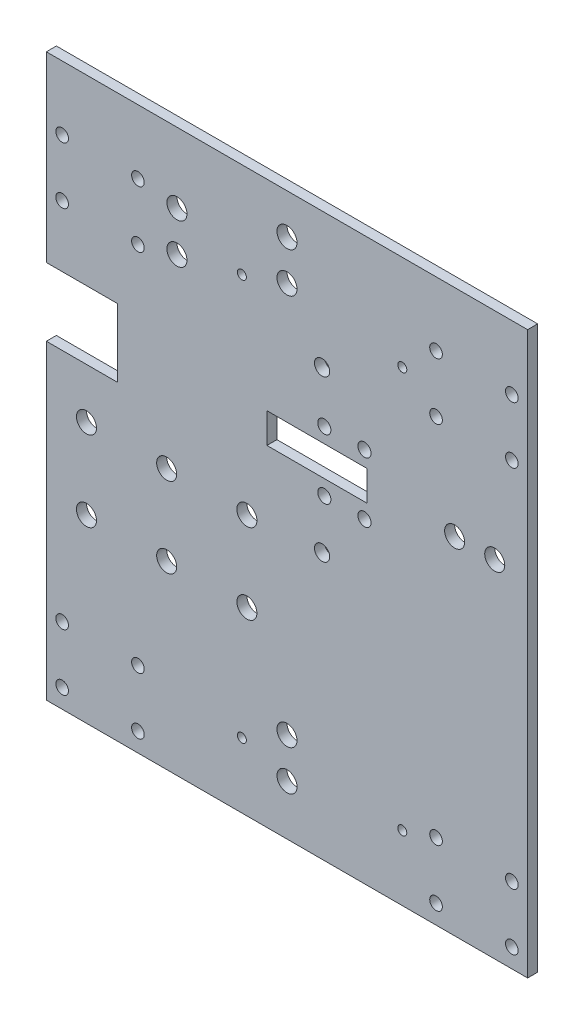
SolidWorks part; units mm, degrees
ref_plane "Front Plane" through (0, 0, 0) normal (0, 0, 1) x (1, 0, 0)
ref_plane "Top Plane" through (0, 0, 0) normal (0, 1, 0) x (1, 0, 0)
ref_plane "Right Plane" through (0, 0, 0) normal (1, 0, 0) x (0, 0, -1)
sketch "Sketch1" plane through (0, 0, 0) normal (0, 0, 1) x (1, 0, 0)
  line L0 (76.2, 177.8) -> (76.2, 0) construction
  line L1 (0, 0) -> (152.4, 0)
  line L2 (0, 0) -> (0, 98.425)
  line L3 (0, 177.8) -> (152.4, 177.8)
  line L4 (152.4, 0) -> (152.4, 177.8)
  line L5 (38.1, 82.55) -> (63.5, 82.55) construction
  line L6 (101.6, 104.775) -> (69.85, 104.775)
  line L7 (101.6, 104.775) -> (101.6, 114.3)
  line L8 (101.6, 114.3) -> (69.85, 114.3)
  line L9 (69.85, 104.775) -> (69.85, 114.3)
  line L10 (38.1, 57.15) -> (63.5, 57.15) construction
  line L11 (50.8, 82.55) -> (50.8, 57.15) construction
  line L12 (101.6, 109.5375) -> (135.289, 109.5375) construction
  line L13 (69.85, 109.5375) -> (101.6, 109.5375) construction
  line L14 (87.3125, 114.3) -> (87.3125, 104.775) construction
  line L15 (0, 98.425) -> (22.5184, 98.425)
  line L16 (22.5184, 98.425) -> (22.5184, 120.015)
  line L17 (22.5184, 120.015) -> (0, 120.015)
  line L18 (0, 120.015) -> (0, 177.8)
  circle A0 centre (38.1, 82.55) radius 3.175
  circle A1 centre (63.5, 82.55) radius 3.175
  circle A2 centre (38.1, 57.15) radius 3.175
  circle A3 centre (63.5, 57.15) radius 3.175
  circle A4 centre (88.0237, 100.0125) radius 2.0828
  circle A5 centre (100.7237, 100.0125) radius 2.0828
  circle A6 centre (88.0237, 119.0625) radius 2.0828
  circle A7 centre (100.7237, 119.0625) radius 2.0828
  circle A8 centre (129.286, 109.5375) radius 3.175
  circle A9 centre (123.4, 139.48) radius 2
  circle A10 centre (147.4, 139.48) radius 2
  circle A11 centre (123.4, 157.48) radius 2
  circle A12 centre (147.4, 157.48) radius 2
  circle A13 centre (5, 6) radius 2
  circle A14 centre (29, 6) radius 2
  circle A15 centre (5, 24) radius 2
  circle A16 centre (29, 24) radius 2
  circle A17 centre (5, 139.48) radius 2
  circle A18 centre (29, 139.48) radius 2
  circle A19 centre (5, 157.48) radius 2
  circle A20 centre (29, 157.48) radius 2
  circle A21 centre (123.4, 6) radius 2
  circle A22 centre (147.4, 6) radius 2
  circle A23 centre (123.4, 24) radius 2
  circle A24 centre (147.4, 24) radius 2
  circle A25 centre (41.35, 155.575) radius 3.175
  circle A26 centre (41.35, 142.875) radius 3.175
  circle A27 centre (12.7, 57.15) radius 3.175
  circle A28 centre (12.7, 82.55) radius 3.175
  circle A29 centre (141.986, 109.5375) radius 3.175
  circle A30 centre (87.3125, 84.1375) radius 2.413
  circle A31 centre (87.3125, 134.9375) radius 2.413
  circle A32 centre (61.9125, 147.6375) radius 1.4224
  circle A33 centre (112.7125, 147.6375) radius 1.4224
  circle A34 centre (112.7125, 20.6375) radius 1.4224
  circle A35 centre (61.9125, 20.6375) radius 1.4224
  circle A36 centre (76.2, 28.575) radius 3.175
  circle A37 centre (76.2, 15.875) radius 3.175
  circle A38 centre (76.2, 165.1) radius 3.175
  circle A39 centre (76.2, 152.4) radius 3.175
  dimension "D4" = 6.35
  dimension "D7" = 57.15
  dimension "D10" = 24
  dimension "D12" = 4
  dimension "D15" = 4
  dimension "D8" = 38.1
  dimension "D9" = 4
  dimension "D18" = 4
  dimension "D25" = 6.35
  dimension "D29" = 6.35
  dimension "D37" = 4.1656
  dimension "D39" = 18.1737
  dimension "D42" = 6.35
  dimension "D43" = 12.7
  dimension "D44" = 27.686
  dimension "D45" = 4.826
  dimension "D49" = 2.8448
  dimension "D54" = 6.35
  dimension "D57" = 15.875
  dimension "D30" = 25.4
  dimension "D32" = 95.25
  dimension "D60" = 15.875
  dimension "D31" = 6.35
  dimension "D1" = 152.4
  dimension "D2" = 177.8
  dimension "D5" = 25.4
  dimension "D6" = 25.4
  dimension "D11" = 18
  dimension "D13" = 24
  dimension "D14" = 18
  dimension "D16" = 24
  dimension "D17" = 18
  dimension "D19" = 24
  dimension "D20" = 18
  dimension "D21" = 5
  dimension "D22" = 5
  dimension "D23" = 6
  dimension "D24" = 20.32
  dimension "D26" = 12.7
  dimension "D27" = 22.225
  dimension "D28" = 12.35
  dimension "D33" = 31.75
  dimension "D34" = 9.525
  dimension "D35" = 19.05
  dimension "D36" = 22.225
  dimension "D38" = 12.7
  dimension "D40" = 4.7625
  dimension "D41" = 4.7625
  dimension "D46" = 50.8
  dimension "D47" = 50.8
  dimension "D48" = 14.2875
  dimension "D50" = 14.2875
  dimension "D51" = 127
  dimension "D52" = 38.1
  dimension "D53" = 50.8
  dimension "D55" = 12.7
  dimension "D56" = 12.7
  dimension "D58" = 12.7
  dimension "D59" = 25.4
  dimension "D61" = 21.59
extrude "Boss-Extrude1" add sketch "Sketch1" along normal blind 3.175
